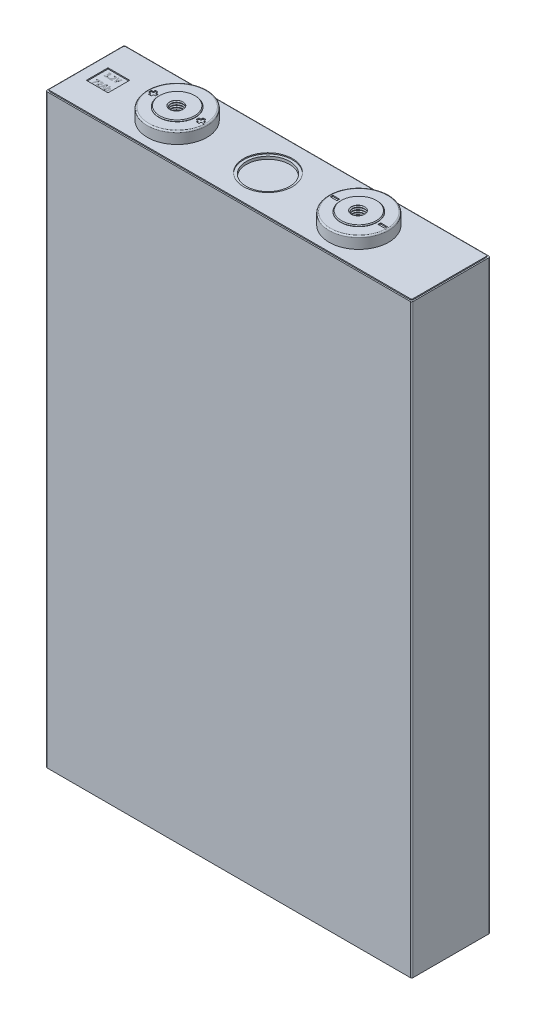
SolidWorks part; units mm, degrees
ref_plane "Front Plane" through (0, 0, 0) normal (0, 0, 1) x (1, 0, 0)
ref_plane "Top Plane" through (0, 0, 0) normal (0, 1, 0) x (1, 0, 0)
ref_plane "Right Plane" through (0, 0, 0) normal (1, 0, 0) x (0, 0, -1)
sketch "Sketch1" plane through (0, 0, 0) normal (0, 1, 0) x (1, 0, 0)
  line L1 (-67.5, -14.5) -> (67.5, -14.5)
  line L2 (-67.5, -14.5) -> (-67.5, 14.5)
  line L3 (-67.5, 14.5) -> (67.5, 14.5)
  line L4 (67.5, -14.5) -> (67.5, 14.5)
  line L5 (-67.5, -14.5) -> (67.5, 14.5) construction
  line L6 (-67.5, 14.5) -> (67.5, -14.5) construction
  point P0 (0, 0)
  dimension "D1" = 135
  dimension "D2" = 29
extrude "Boss-Extrude1" add sketch "Sketch1" along normal blind 216
sketch "Sketch2" plane through (0, 0, 0) normal (0, -1, 0) x (-1, 0, 0)
  line L0 (0, -14.5) -> (0, 0) construction
  line L1 (67.5, -14.5) -> (-67.5, -14.5) construction
  line L2 (67.5, 14.5) -> (67.5, -14.5) construction
  line L3 (67, 14) -> (-67, 14)
  line L4 (67, 14) -> (67, -14)
  line L5 (67, -14) -> (-67, -14)
  line L6 (-67, 14) -> (-67, -14)
  line L7 (67, 14) -> (-67, -14) construction
  line L8 (67, -14) -> (-67, 14) construction
  dimension "D1" = 0.5
  dimension "D2" = 0.5
extrude "Boss-Extrude2" add sketch "Sketch2" along normal blind 0.4
ref_plane "Plane1" through (0, 108, 0) normal (0, 1, 0) x (1, 0, 0)
mirror "Mirror1" about plane through (0, 108, 0) normal (0, 1, 0) of "Boss-Extrude2"
sketch "Sketch3" plane through (0, 216.4, 0) normal (0, 1, 0) x (1, 0, 0)
  circle A0 centre (0, 0) radius 9
  dimension "D1" = 18
extrude "Cut-Extrude1" cut sketch "Sketch3" against normal blind 0.4
sketch "Sketch4" plane through (0, 216, 0) normal (0, 1, 0) x (1, 0, 0)
  circle A0 centre (0, 0) radius 8
  dimension "D1" = 16
extrude "Cut-Extrude2" cut sketch "Sketch4" against normal blind 1
sketch "Sketch6" plane through (0, 216.4, 0) normal (0, 1, 0) x (1, 0, 0)
  line L0 (0, 0) -> (-67, 0) construction
  line L1 (-67, -14) -> (-67, 14) construction
  line L2 (0, 0) -> (0, 14.7883) construction
  circle A0 centre (-33.5, 0) radius 11
  circle A1 centre (33.5, 0) radius 11
  dimension "D1" = 22
extrude "Boss-Extrude4" add sketch "Sketch6" along normal blind 4.25
sketch "Sketch7" plane through (0, 220.65, 0) normal (0, 1, 0) x (1, 0, 0)
  circle A0 centre (-33.5, 0) radius 6.75
  circle A1 centre (33.5, 0) radius 6.75
  dimension "D1" = 13.5
  dimension "D2" = 13.5
extrude "Boss-Extrude5" add sketch "Sketch7" along normal blind 0.4
sketch "Sketch8" plane through (0, 221.05, 0) normal (0, 1, 0) x (1, 0, 0)
  circle A0 centre (33.5, 0) radius 2.25
  circle A1 centre (-33.5, 0) radius 2.25
  dimension "D1" = 4.5
  dimension "D2" = 4.5
extrude "Cut-Extrude3" cut sketch "Sketch8" against normal blind 8
thread "Thread1" pitch 0.8 method cut profile "Thread Profile1" start angle 0, offset 0, length 8, pitch 0.8, diameter 4.5
ref_plane "Plane2" through (35.75, 213.05, 0) normal (0, 0, 1) x (1, 0, 0)
sketch "Thread Profile1" plane through (35.75, 213.05, 0) normal (0, 0, 1) x (1, 0, 0)
  line L0 (0, 0) -> (0, 0.8) construction
  line L1 (0, 0) -> (0.433, 0.25)
  line L2 (0.433, 0.25) -> (0.433, 0.35)
  line L3 (0.433, 0.35) -> (0, 0.6)
  line L4 (0.433, 0.3) -> (0, 0.3) construction
  line L11 (0, 0) -> (0, 0.6)
  point P2 (0, 0)
  dimension "Pitch" = 0.8
  dimension "Profile_Angle" = 60
  dimension "Profile_Land" = 0.1
  dimension "Profile_Height" = 0.433
thread "Thread2" pitch 0.8 method cut profile "Thread Profile2" start angle 0, offset 0, length 8, pitch 0.8, diameter 4.5
ref_plane "Plane3" through (-31.25, 213.05, 0) normal (0, 0, 1) x (1, 0, 0)
sketch "Thread Profile2" plane through (-31.25, 213.05, 0) normal (0, 0, 1) x (1, 0, 0)
  line L0 (0, 0) -> (0, 0.8) construction
  line L1 (0, 0) -> (0.433, 0.25)
  line L2 (0.433, 0.25) -> (0.433, 0.35)
  line L3 (0.433, 0.35) -> (0, 0.6)
  line L4 (0.433, 0.3) -> (0, 0.3) construction
  line L11 (0, 0) -> (0, 0.6)
  point P2 (0, 0)
  dimension "Pitch" = 0.8
  dimension "Profile_Angle" = 60
  dimension "Profile_Land" = 0.1
  dimension "Profile_Height" = 0.433
chamfer "Chamfer1" distance 0.3 angle 45 2 edges at (-33.5, 221.05, 6.75) (33.5, 221.05, 6.75)
fillet "Fillet1" radius 0.5 2 edges at (33.5, 220.65, -11) (-33.5, 220.65, 11)
fillet "Fillet2" radius 0.5 4 edges at (-67.5, 108, -14.5) (-67.5, 108, 14.5) (67.5, 108, 14.5) (67.5, 108, -14.5)
fillet "Fillet3" radius 0.5 8 edges at (-67, -0.2, 14) (-67, -0.2, -14) (67, -0.2, 14) (67, -0.2, -14) (67, 216.2, 14) (67, 216.2, -14) (-67, 216.2, -14) (-67, 216.2, 14)
sketch "Sketch15" plane through (0, 220.65, 0) normal (0, 1, 0) x (1, 0, 0)
  line L0 (0, 0) -> (44, 0) construction
  line L1 (33.5, 0) -> (33.5, 6.1736) construction
  line L2 (43.45, 0.5) -> (41.15, 0.5)
  line L3 (43.55, 0.4) -> (43.55, -0.4)
  line L4 (43.45, -0.5) -> (41.15, -0.5)
  line L5 (41.05, 0.4) -> (41.05, -0.4)
  line L6 (43.55, 0.5) -> (41.05, -0.5) construction
  line L7 (43.55, -0.5) -> (41.05, 0.5) construction
  line L8 (23.45, -0.5) -> (25.95, 0.5) construction
  line L9 (23.45, 0.5) -> (25.95, -0.5) construction
  line L10 (25.95, 0.4) -> (25.95, -0.4)
  line L11 (23.55, -0.5) -> (25.85, -0.5)
  line L12 (23.45, 0.4) -> (23.45, -0.4)
  line L13 (23.55, 0.5) -> (25.85, 0.5)
  line L14 (0, 0) -> (0, 6.9697) construction
  line L15 (-33.5, 0) -> (-33.5, 10.5) construction
  line L16 (-25.2, 1.25) -> (-24.2, -1.25) construction
  line L17 (-43.55, -0.5) -> (-41.05, 0.5) construction
  line L18 (-43.55, 0.5) -> (-41.05, -0.5) construction
  line L23 (-41.05, 0.4) -> (-41.05, -0.4)
  line L24 (-43.45, -0.5) -> (-42.9, -0.5)
  line L25 (-43.55, 0.4) -> (-43.55, -0.4)
  line L26 (-43.45, 0.5) -> (-42.9, 0.5)
  line L27 (-41.7, -0.5) -> (-41.15, -0.5)
  line L28 (-41.9, -1.25) -> (-42.7, -1.25)
  line L29 (-41.8, -1.15) -> (-41.8, -0.6)
  line L30 (-41.9, 1.25) -> (-42.7, 1.25)
  line L31 (-42.8, -1.15) -> (-42.8, -0.6)
  line L32 (-41.8, -1.25) -> (-42.8, 1.25) construction
  line L33 (-41.8, 1.25) -> (-42.8, -1.25) construction
  line L34 (-41.7, 0.5) -> (-41.15, 0.5)
  line L35 (-41.8, 0.6) -> (-41.8, 1.15)
  line L36 (-42.8, 0.6) -> (-42.8, 1.15)
  line L37 (-25.2, -1.25) -> (-24.2, 1.25) construction
  line L38 (-23.45, 0.5) -> (-25.95, -0.5) construction
  line L39 (-23.45, -0.5) -> (-25.95, 0.5) construction
  line L40 (-24.2, 0.6) -> (-24.2, 1.15)
  line L41 (-25.2, 0.6) -> (-25.2, 1.15)
  line L42 (-25.3, 0.5) -> (-25.85, 0.5)
  line L43 (-24.2, -1.15) -> (-24.2, -0.6)
  line L44 (-25.1, 1.25) -> (-24.3, 1.25)
  line L45 (-25.2, -1.15) -> (-25.2, -0.6)
  line L46 (-25.1, -1.25) -> (-24.3, -1.25)
  line L47 (-25.3, -0.5) -> (-25.85, -0.5)
  line L48 (-23.55, 0.5) -> (-24.1, 0.5)
  line L49 (-23.45, 0.4) -> (-23.45, -0.4)
  line L50 (-23.55, -0.5) -> (-24.1, -0.5)
  line L51 (-25.95, 0.4) -> (-25.95, -0.4)
  circle A0 centre (33.5, 0) radius 10.5 construction
  arc A1 (41.15, 0.5) -> (41.05, 0.4) centre (41.15, 0.4) ccw
  arc A2 (41.15, -0.5) -> (41.05, -0.4) centre (41.15, -0.4) cw
  arc A3 (43.45, 0.5) -> (43.55, 0.4) centre (43.45, 0.4) cw
  arc A4 (43.55, -0.4) -> (43.45, -0.5) centre (43.45, -0.4) cw
  arc A5 (23.45, -0.4) -> (23.55, -0.5) centre (23.55, -0.4) ccw
  arc A6 (23.55, 0.5) -> (23.45, 0.4) centre (23.55, 0.4) ccw
  arc A7 (25.85, -0.5) -> (25.95, -0.4) centre (25.85, -0.4) ccw
  arc A8 (25.85, 0.5) -> (25.95, 0.4) centre (25.85, 0.4) cw
  arc A13 (-43.55, -0.4) -> (-43.45, -0.5) centre (-43.45, -0.4) ccw
  arc A14 (-43.45, 0.5) -> (-43.55, 0.4) centre (-43.45, 0.4) ccw
  arc A15 (-41.15, -0.5) -> (-41.05, -0.4) centre (-41.15, -0.4) ccw
  arc A16 (-41.15, 0.5) -> (-41.05, 0.4) centre (-41.15, 0.4) cw
  arc A17 (-42.7, 1.25) -> (-42.8, 1.15) centre (-42.7, 1.15) ccw
  arc A18 (-41.8, 1.15) -> (-41.9, 1.25) centre (-41.9, 1.15) ccw
  arc A19 (-42.7, -1.25) -> (-42.8, -1.15) centre (-42.7, -1.15) cw
  arc A20 (-41.9, -1.25) -> (-41.8, -1.15) centre (-41.9, -1.15) ccw
  arc A21 (-41.7, 0.5) -> (-41.8, 0.6) centre (-41.7, 0.6) cw
  arc A22 (-42.9, 0.5) -> (-42.8, 0.6) centre (-42.9, 0.6) ccw
  arc A23 (-42.9, -0.5) -> (-42.8, -0.6) centre (-42.9, -0.6) cw
  arc A24 (-41.7, -0.5) -> (-41.8, -0.6) centre (-41.7, -0.6) ccw
  circle A25 centre (-33.5, 0) radius 10.5 construction
  arc A26 (-25.3, -0.5) -> (-25.2, -0.6) centre (-25.3, -0.6) cw
  arc A27 (-24.1, -0.5) -> (-24.2, -0.6) centre (-24.1, -0.6) ccw
  arc A28 (-24.1, 0.5) -> (-24.2, 0.6) centre (-24.1, 0.6) cw
  arc A29 (-25.3, 0.5) -> (-25.2, 0.6) centre (-25.3, 0.6) ccw
  arc A30 (-25.1, -1.25) -> (-25.2, -1.15) centre (-25.1, -1.15) cw
  arc A31 (-24.3, -1.25) -> (-24.2, -1.15) centre (-24.3, -1.15) ccw
  arc A32 (-25.2, 1.15) -> (-25.1, 1.25) centre (-25.1, 1.15) cw
  arc A33 (-24.3, 1.25) -> (-24.2, 1.15) centre (-24.3, 1.15) cw
  arc A34 (-25.85, 0.5) -> (-25.95, 0.4) centre (-25.85, 0.4) ccw
  arc A35 (-25.85, -0.5) -> (-25.95, -0.4) centre (-25.85, -0.4) cw
  arc A36 (-23.55, 0.5) -> (-23.45, 0.4) centre (-23.55, 0.4) cw
  arc A37 (-23.45, -0.4) -> (-23.55, -0.5) centre (-23.55, -0.4) cw
  point P6 (42.3, 0)
  point P42 (24.7, 0)
  point P77 (-42.3, 0)
  point P78 (-42.3, 0)
  point P101 (-41.8, 0.5)
  point P104 (-42.8, 0.5)
  point P142 (-24.2, 0.5)
  point P143 (-25.2, 0.5)
  point P144 (-24.7, 0)
  dimension "D4" = 0.1
  dimension "D7" = 0.1
  dimension "D8" = 0.1
  dimension "D1" = 2.5
  dimension "D2" = 1
  dimension "D3" = 1.7
  dimension "D5" = 1
  dimension "D6" = 2.5
extrude "Cut-Extrude4" cut sketch "Sketch15" against normal blind 0.4
sketch "Sketch16" plane through (0, 216.4, 0) normal (0, 1, 0) x (1, 0, 0)
  line L0 (-67, 0) -> (-59, 0) construction
  line L1 (-67, -13.5) -> (-67, 13.5) construction
  line L3 (-55.2, 4) -> (-62.8, 4)
  line L4 (-55, 3.8) -> (-55, -3.8)
  line L5 (-55.2, -4) -> (-62.8, -4)
  line L6 (-63, 3.8) -> (-63, -3.8)
  line L7 (-55, 4) -> (-63, -4) construction
  line L8 (-55, -4) -> (-63, 4) construction
  arc A0 (-63, 3.8) -> (-62.8, 4) centre (-62.8, 3.8) cw
  arc A1 (-55.2, 4) -> (-55, 3.8) centre (-55.2, 3.8) cw
  arc A2 (-63, -3.8) -> (-62.8, -4) centre (-62.8, -3.8) ccw
  arc A3 (-55.2, -4) -> (-55, -3.8) centre (-55.2, -3.8) ccw
  dimension "D4" = 0.2
  dimension "D1" = 8
  dimension "D2" = 8
  dimension "D3" = 8
extrude "Cut-Extrude5" cut sketch "Sketch16" against normal blind 0.4
sketch "Sketch17" plane through (0, 216, 0) normal (0, 1, 0) x (1, 0, 0)
  text T0 "3.2V\r\n72Ah\r\n" font "Adobe Heiti Std R" height 2
extrude "Boss-Extrude6" add sketch "Sketch17" along normal blind 0.01
scale "Scale2" bodies to scale 114 scale about centroid uniform scaling yes scale factor 0.6
